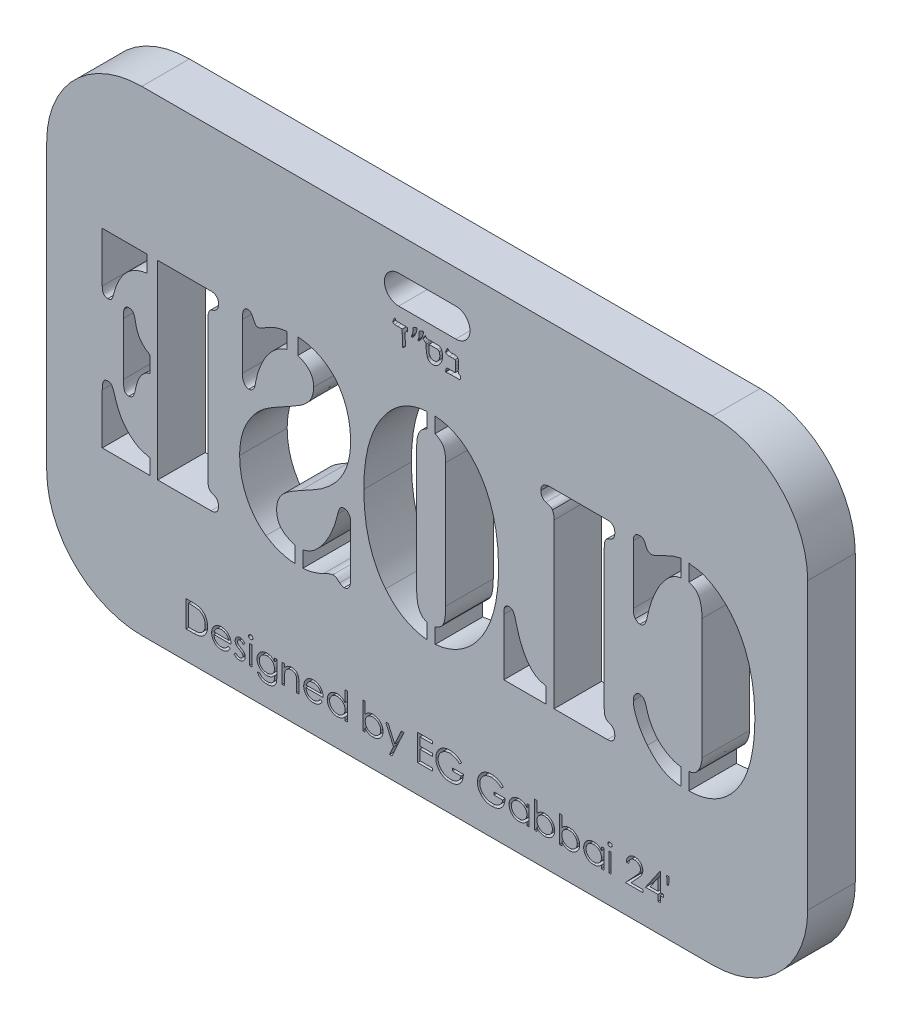
SolidWorks part; units mm, degrees
ref_plane "Front Plane" through (0, 0, 0) normal (0, 0, 1) x (1, 0, 0)
ref_plane "Top Plane" through (0, 0, 0) normal (0, 1, 0) x (1, 0, 0)
ref_plane "Right Plane" through (0, 0, 0) normal (1, 0, 0) x (0, 0, -1)
sketch "Sketch1" plane through (0, 0, 0) normal (0, 0, 1) x (1, 0, 0)
  line L1 (-88.9, 63.5) -> (-12.7, 63.5)
  line L2 (-101.6, 50.8) -> (-101.6, 12.7)
  line L3 (-88.9, 0) -> (-12.7, 0)
  line L4 (0, 50.8) -> (0, 12.7)
  arc A0 (-12.7, 0) -> (0, 12.7) centre (-12.7, 12.7) ccw
  arc A1 (-101.6, 12.7) -> (-88.9, 0) centre (-88.9, 12.7) ccw
  arc A2 (-12.7, 63.5) -> (0, 50.8) centre (-12.7, 50.8) cw
  arc A3 (-88.9, 63.5) -> (-101.6, 50.8) centre (-88.9, 50.8) ccw
  point P7 (0, 0)
  point P10 (-101.6, 0)
  point P13 (0, 63.5)
  point P16 (-101.6, 63.5)
  dimension "D3" = 12.7
  dimension "D4" = 12.7
  dimension "D5" = 12.7
  dimension "D6" = 12.7
  dimension "D1" = 101.6
  dimension "D2" = 63.5
extrude "Boss-Extrude1" add sketch "Sketch1" along normal blind 6.35
sketch "Sketch2" plane through (0, 0, 6.35) normal (0, 0, 1) x (1, 0, 0)
  line L1 (-88.9, 0) -> (-12.7, 0) construction
  line L2 (0, 12.7) -> (0, 50.8) construction
  text T0 "Close" font "Stencil" height 25.4
  point P1 (0, 0)
  dimension "D1" = 6.35
  dimension "D2" = 19.05
extrude "Cut-Extrude1" cut sketch "Sketch2" against normal blind 6.35
sketch "Sketch3" plane through (0, 0, 6.35) normal (0, 0, 1) x (1, 0, 0)
  line L0 (-54.61, 57.15) -> (-46.99, 57.15) construction
  line L1 (-54.61, 59.055) -> (-46.99, 59.055)
  line L2 (-54.61, 55.245) -> (-46.99, 55.245)
  line L3 (-101.6, 50.8) -> (-101.6, 12.7) construction
  line L6 (-12.7, 63.5) -> (-88.9, 63.5) construction
  arc A0 (-54.61, 59.055) -> (-54.61, 55.245) centre (-54.61, 57.15) ccw
  arc A1 (-46.99, 55.245) -> (-46.99, 59.055) centre (-46.99, 57.15) ccw
  point P2 (-50.8, 57.15)
  point P16 (-50.8, 63.5)
  dimension "D1" = 50.8
  dimension "D2" = 6.35
  dimension "D3" = 3.81
  dimension "D4" = 7.62
extrude "Cut-Extrude2" cut sketch "Sketch3" against normal blind 6.35
sketch "Sketch4" plane through (0, 0, 6.35) normal (0, 0, 1) x (1, 0, 0)
  line L0 (-97.8803, 3.7197) -> (-3.7197, 3.7197) construction
  line L1 (-101.6, 50.8) -> (0, 50.8) construction
  arc A0 (-101.6, 12.7) -> (-88.9, 0) centre (-88.9, 12.7) ccw construction
  arc A1 (-12.7, 0) -> (0, 12.7) centre (-12.7, 12.7) ccw construction
  text T0 "בס״ד" font "Narkisim" height 3.5
  text T1 "Designed by EG Gabbai 24'"
  point P15 (-50.8, 50.8)
extrude "Cut-Extrude3" cut sketch "Sketch4" against normal blind 2.54
